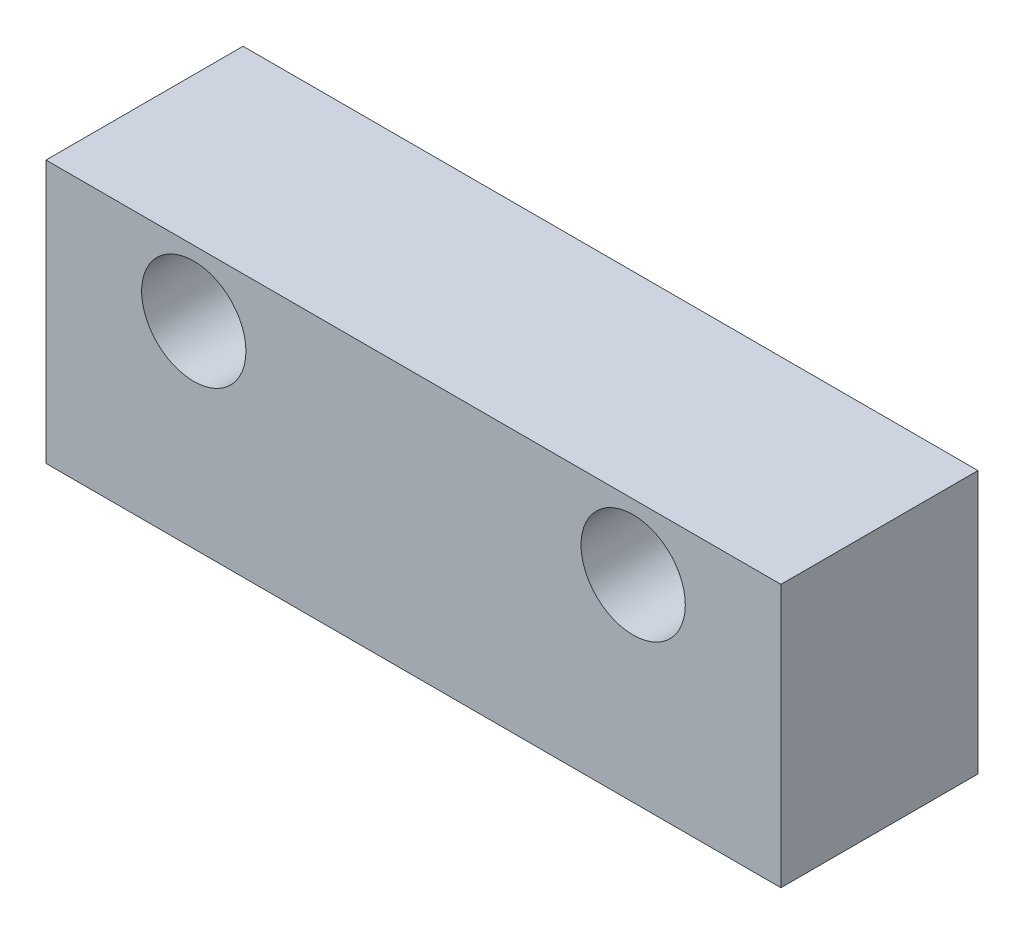
SolidWorks part; units mm, degrees
material "Plain Carbon Steel"
ref_plane "Front Plane" through (0, 0, 0) normal (0, 0, 1) x (1, 0, 0)
ref_plane "Top Plane" through (0, 0, 0) normal (0, 1, 0) x (1, 0, 0)
ref_plane "Right Plane" through (0, 0, 0) normal (1, 0, 0) x (0, 0, -1)
sketch "Sketch1" plane through (0, 0, 0) normal (0, 0, 1) x (1, 0, 0)
  line L0 (-22.375, -12) -> (22.375, -12)
  line L1 (22.375, -12) -> (22.375, 4)
  line L2 (22.375, 4) -> (-22.375, 4)
  line L3 (-22.375, 4) -> (-22.375, -12)
  circle A0 centre (13.377, 0) radius 3.175
  circle A1 centre (-13.377, 0) radius 3.175
  dimension "D1" = 6.35
  dimension "D2" = 6.35
extrude "Boss-Extrude1" add sketch "Sketch1" along normal blind 12
